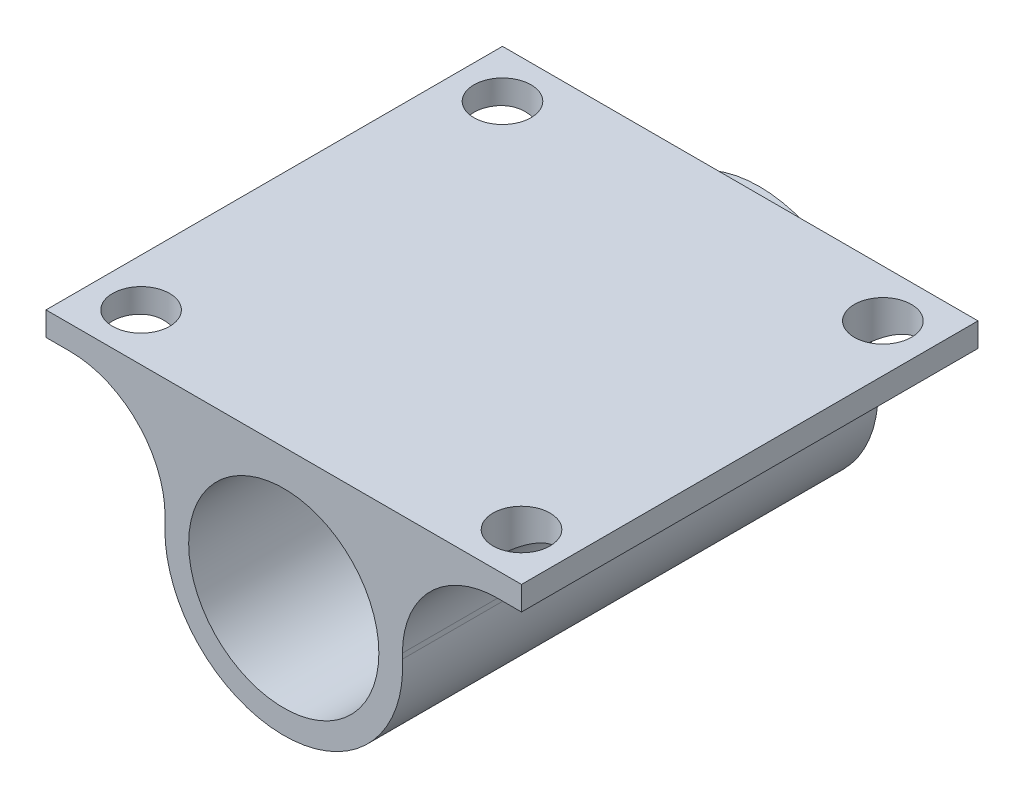
SolidWorks part; units mm, degrees
ref_plane "Front" through (0, 0, 0) normal (0, 0, 1) x (1, 0, 0)
ref_plane "Top" through (0, 0, 0) normal (0, 1, 0) x (1, 0, 0)
ref_plane "Right" through (0, 0, 0) normal (1, 0, 0) x (0, 0, -1)
sketch "Sketch1" plane through (0, 0, 0) normal (0, 0, 1) x (1, 0, 0)
  line L2 (-25, 11.2434) -> (-25, 13.7566)
  line L3 (-25, 13.7566) -> (25, 13.7566)
  line L4 (25, 11.2434) -> (25, 13.7566)
  line L5 (0, 12.5) -> (-25, 12.5) construction
  line L6 (0, 12.5) -> (25, 12.5) construction
  line L7 (25, 11.2434) -> (22.4809, 11.2434)
  line L8 (12.4809, 1.2434) -> (12.4809, 0.6908)
  line L9 (-12.4809, 0.6908) -> (-12.4809, 1.2434)
  line L10 (-22.4809, 11.2434) -> (-25, 11.2434)
  circle A0 centre (0, 0) radius 10
  arc A1 (-12.4809, 0.6908) -> (12.4809, 0.6908) centre (0, 0) ccw
  arc A4 (22.4809, 11.2434) -> (12.4809, 1.2434) centre (22.4809, 1.2434) ccw
  arc A5 (-12.4809, 1.2434) -> (-22.4809, 11.2434) centre (-22.4809, 1.2434) ccw
  point P4 (0, 12.5)
  point P12 (5.4623, 11.2434)
  dimension "D1" = 20
  dimension "D2" = 25
  dimension "D4" = 10
  dimension "D3" = 50
extrude "Boss-Extrude1" add sketch "Sketch1" along normal blind 48
sketch "Sketch3" plane through (0, 0, 0) normal (0, 0, -1) x (-1, 0, 0)
  line L0 (-7.5, 0) -> (7.5, 0) construction
  circle A0 centre (0, 0) radius 3.5
  circle A1 centre (0, 0) radius 12.5
  circle A2 centre (7.5, 0) radius 0.95
  circle A3 centre (-7.5, 0) radius 0.95
  point P8 (0, 0)
  dimension "D1" = 7
  dimension "D2" = 25
  dimension "D3" = 1.9
  dimension "D4" = 1.9
  dimension "D5" = 7.5
  dimension "D6" = 7.5
extrude "Boss-Extrude3" add sketch "Sketch3" along normal blind 2
sketch "Sketch4" plane through (0, 13.7566, 0) normal (0, 1, 0) x (1, 0, 0)
  line L0 (25, -48) -> (25, 0) construction
  line L1 (25, 0) -> (-25, 0) construction
  line L2 (-25, -48) -> (-25, 0) construction
  line L3 (25, -48) -> (-25, -48) construction
  circle A0 centre (-20, -5) radius 3
  circle A1 centre (20, -5) radius 3
  circle A2 centre (20, -43) radius 3
  circle A3 centre (-20, -43) radius 3
  dimension "D1" = 6
  dimension "D2" = 6
  dimension "D3" = 6
  dimension "D4" = 6
  dimension "D5" = 5
  dimension "D6" = 5
  dimension "D7" = 5
  dimension "D8" = 5
  dimension "D9" = 5
  dimension "D10" = 5
  dimension "D11" = 5
  dimension "D12" = 5
extrude "Cut-Extrude1" cut sketch "Sketch4" against normal through all
